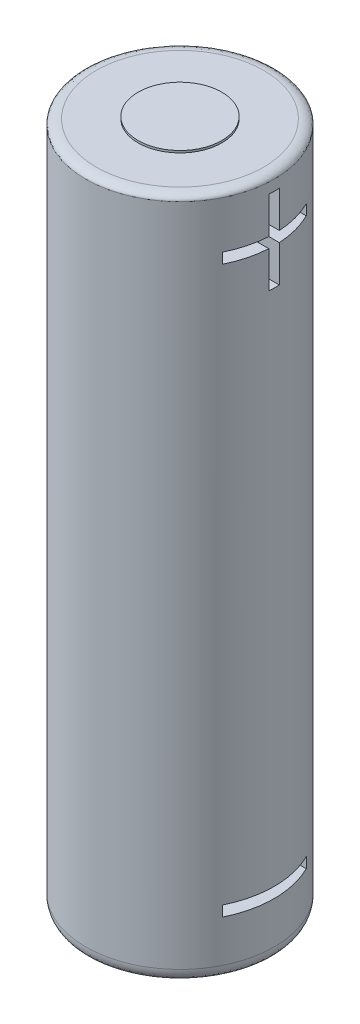
SolidWorks part; units mm, degrees
ref_plane "Front Plane" through (0, 0, 0) normal (0, 0, 1) x (1, 0, 0)
ref_plane "Top Plane" through (0, 0, 0) normal (0, 1, 0) x (1, 0, 0)
ref_plane "Right Plane" through (0, 0, 0) normal (1, 0, 0) x (0, 0, -1)
sketch "Sketch1" plane through (0, 0, 0) normal (0, 1, 0) x (1, 0, 0)
  circle A0 centre (0, 0) radius 9
  dimension "D1" = 18
extrude "Boss-Extrude1" add sketch "Sketch1" along normal mid plane 65
fillet "Fillet1" radius 0.5 2 edges at (0, -32.5, 9) (0, 32.5, 9) second distance 1 first distance on face at (0, -32.5, 9) first distance on face at (0, 32.5, 9)
sketch "Sketch2" plane through (0, -32.5, 0) normal (0, -1, 0) x (1, 0, 0)
  circle A0 centre (0, 0) radius 7
  dimension "D1" = 14
extrude "Cut-Extrude1" cut sketch "Sketch2" against normal blind 0.2
sketch "Sketch3" plane through (0, 32.5, 0) normal (0, 1, 0) x (1, 0, 0)
  circle A0 centre (0, 0) radius 4
  dimension "D1" = 8
extrude "Boss-Extrude2" add sketch "Sketch3" along normal blind 0.2
sketch "Sketch4" plane through (0, 0, 0) normal (1, 0, 0) x (0, 0, -1)
  line L0 (-8.5, -32.5) -> (8.5, -32.5) construction
  line L1 (-4, -26.5) -> (4, -26.5)
  line L2 (-4, -26.5) -> (-4, -27.5)
  line L3 (-4, -27.5) -> (4, -27.5)
  line L4 (4, -26.5) -> (4, -27.5)
  line L5 (0, 0) -> (9, 0) construction
  line L6 (9, -31.5) -> (9, 32) construction
  line L7 (4, 26.5) -> (4, 27.5)
  line L8 (-4, 27.5) -> (4, 27.5)
  line L9 (-4, 26.5) -> (-4, 27.5)
  line L10 (-4, 26.5) -> (4, 26.5)
  line L12 (-0.5, 31) -> (0.5, 31)
  line L13 (-0.5, 31) -> (-0.5, 23)
  line L14 (-0.5, 23) -> (0.5, 23)
  line L15 (0.5, 31) -> (0.5, 23)
  point P4 (0, -26.5)
  point P20 (0, 23)
  point P21 (0, 26.5)
  point P22 (-0.5, 27)
  point P23 (-4, 27)
  dimension "D1" = 8
  dimension "D2" = 1
  dimension "D3" = 5
  dimension "D4" = 1
  dimension "D5" = 8
ref_plane "Plane1" through (9, 0, 0) normal (1, 0, 0) x (0, 0, -1)
sketch "Sketch5" plane through (9, 0, 0) normal (1, 0, 0) x (0, 0, -1)
  line L4 (4, 26.5) -> (4, 27.5)
  line L5 (4, 27.5) -> (-4, 27.5)
  line L6 (-4, 27.5) -> (-4, 26.5)
  line L7 (-4, 26.5) -> (4, 26.5)
  line L8 (4, 26.5) -> (4, 27.5)
  line L9 (4, 27.5) -> (-4, 27.5)
  line L10 (-4, 27.5) -> (-4, 26.5)
  line L11 (-4, 26.5) -> (4, 26.5)
  line L12 (4, -26.5) -> (-4, -26.5)
  line L13 (4, -27.5) -> (4, -26.5)
  line L14 (-4, -27.5) -> (4, -27.5)
  line L15 (-4, -26.5) -> (-4, -27.5)
  line L16 (4, -26.5) -> (-4, -26.5)
  line L17 (4, -27.5) -> (4, -26.5)
  line L18 (-4, -27.5) -> (4, -27.5)
  line L19 (-4, -26.5) -> (-4, -27.5)
  line L20 (0.5, 31) -> (-0.5, 31)
  line L21 (0.5, 23) -> (0.5, 31)
  line L22 (-0.5, 23) -> (0.5, 23)
  line L23 (-0.5, 31) -> (-0.5, 23)
  line L24 (0.5, 31) -> (-0.5, 31)
  line L25 (0.5, 23) -> (0.5, 31)
  line L26 (-0.5, 23) -> (0.5, 23)
  line L27 (-0.5, 31) -> (-0.5, 23)
  dimension "D1" = 0
  dimension "D2" = 0
  dimension "D3" = 0
extrude "Cut-Extrude2" cut sketch "Sketch5" against normal blind 2 contours L24 L27 L9 L25 | L27 L9 L10 L11 | L9 L27 L11 L25 | L11 L27 L26 L25 | L25 L11 L8 L9 | L16 L19 L18 L17 region at (9, 27, -2.25) region at (9, 24.75, 0) region at (9, 27, 0) region at (9, 29.25, 0) region at (9, 27, 2.25) region at (9, -27, 0)
mirror "Mirror1" about plane through (0, 0, 0) normal (1, 0, 0) of "Cut-Extrude2"
